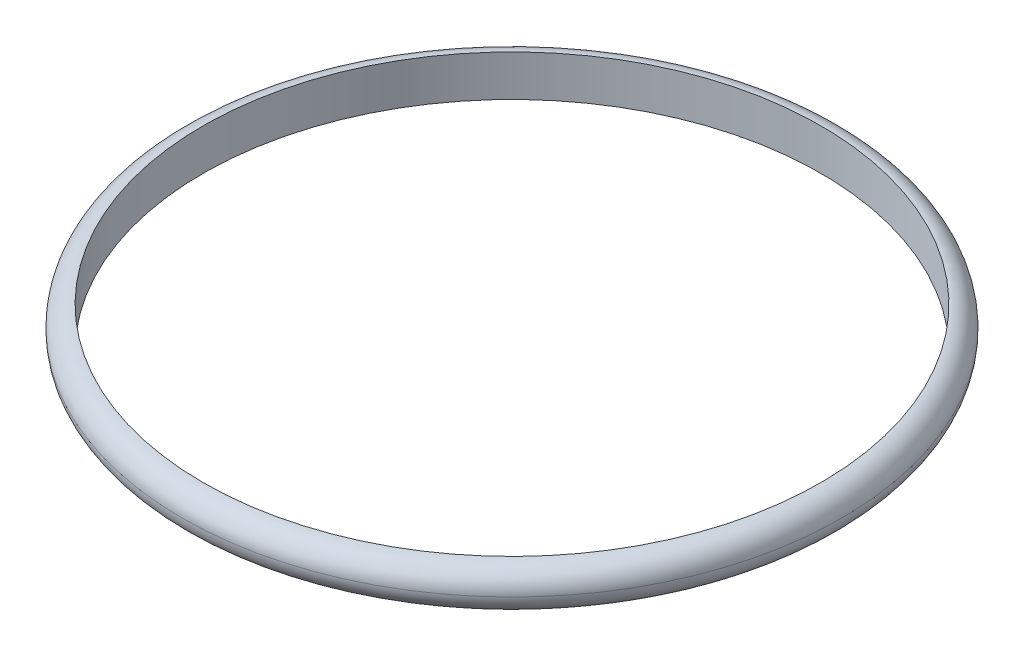
SolidWorks part; units mm, degrees
ref_plane "Face" through (0, 0, 0) normal (0, 0, 1) x (1, 0, 0)
ref_plane "Dessus" through (0, 0, 0) normal (0, 1, 0) x (1, 0, 0)
ref_plane "Droite" through (0, 0, 0) normal (1, 0, 0) x (0, 0, -1)
sketch "Esquisse1" plane through (0, 0, 0) normal (0, 1, 0) x (1, 0, 0)
  circle A0 centre (0, 0) radius 32
  circle A1 centre (0, 0) radius 30
  dimension "D1" = 64
  dimension "D2" = 60
extrude "Extrusion1" add sketch "Esquisse1" along normal blind 4
fillet "Congé1" radius 2 2 edges at (0, 0, 32) (0, 4, 32)
